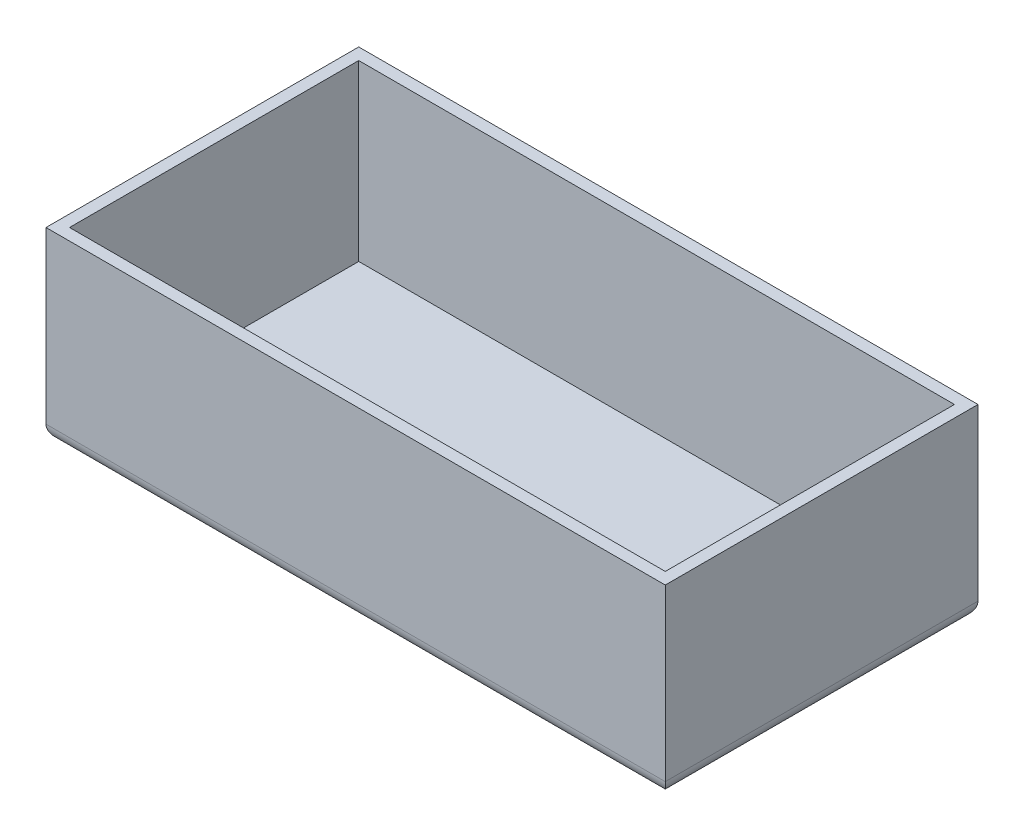
SolidWorks part; units mm, degrees
ref_plane "Alzado" through (0, 0, 0) normal (0, 0, 1) x (1, 0, 0)
ref_plane "Planta" through (0, 0, 0) normal (0, 1, 0) x (1, 0, 0)
ref_plane "Vista lateral" through (0, 0, 0) normal (1, 0, 0) x (0, 0, -1)
sketch "Croquis1" plane through (0, 0, 0) normal (0, 1, 0) x (1, 0, 0)
  line L1 (-100, -50.5) -> (100, -50.5)
  line L2 (-100, -50.5) -> (-100, 50.5)
  line L3 (-100, 50.5) -> (100, 50.5)
  line L4 (100, -50.5) -> (100, 50.5)
  line L5 (-100, -50.5) -> (100, 50.5) construction
  line L6 (-100, 50.5) -> (100, -50.5) construction
  point P0 (0, 0)
  dimension "D1" = 200
  dimension "D2" = 101
extrude "Saliente-Extruir1" add sketch "Croquis1" along normal blind 60
shell "Vaciado1" thickness 3.8 removed face at (0, 60, 0)
fillet "Redondeo3" radius 5 4 edges at (-100, 0, 0) (0, 0, 50.5) (100, 0, 0) (0, 0, -50.5)
